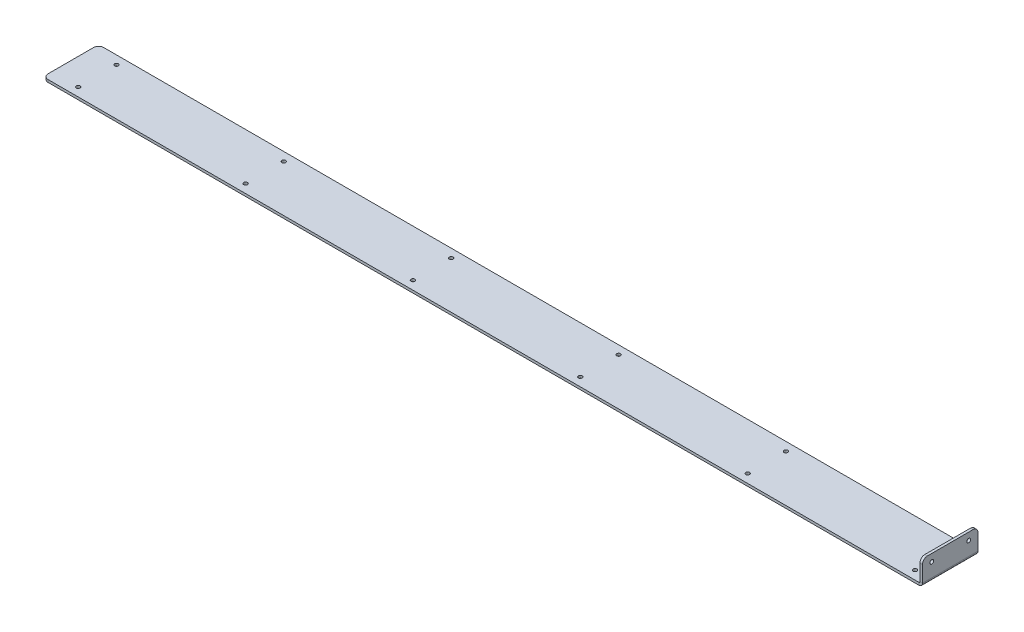
SolidWorks part; units mm, degrees
note: The reader was unsure of these and kept them because the rebuilt part matched: flange length of "Edge-Flange2".
material "5052-H32"
ref_plane "Front Plane" through (0, 0, 0) normal (0, 0, 1) x (1, 0, 0)
ref_plane "Top Plane" through (0, 0, 0) normal (0, 1, 0) x (1, 0, 0)
ref_plane "Right Plane" through (0, 0, 0) normal (1, 0, 0) x (0, 0, -1)
sketch "Sketch1" plane through (0, 0, 0) normal (0, 1, 0) x (1, 0, 0)
  line L1 (-1126.471, 35.7187) -> (0, 35.7188)
  line L2 (-1126.471, 35.7187) -> (-1126.471, -35.7188)
  line L3 (-1126.471, -35.7188) -> (0, -35.7188)
  line L4 (0, 35.7188) -> (0, -35.7188)
  point P4 (0, 0)
  dimension "D1" = 1126.471
  dimension "D2" = 71.4375
base flange "Base-Flange1" sketch "Sketch1" thickness 3.2639 reverse thickness direction no parameters "D1"=1.27
edge flange "Edge-Flange2" sketch "Sketch11" flange angle 90 flange length 31.75 flange position bend outside bend radius 1.27 thickness 3.2639 relief rectangular parameters "D6"=10
sketch "Sketch11" plane through (0, 0, 0) normal (1, 0, 0) x (0, 0, -1)
  line L2 (-35.7188, 0) -> (-35.7188, 28.4861)
  line L3 (-35.7188, 28.4861) -> (35.7187, 28.4861)
  line L4 (35.7187, 28.4861) -> (35.7188, 0)
  line L7 (-35.7188, 0) -> (35.7188, 0) construction
  line L8 (-35.7188, 0) -> (35.7188, 0)
bend "EdgeBend2" bend radius 1.27 bend angle 90 parameters "D5"=2
sketch "Sketch12" plane through (0, 0, 0) normal (0, 1, 0) x (1, 0, 0)
  line L0 (-16.1036, 24.6062) -> (-16.1036, -24.6062) construction
  line L1 (4.5339, 35.7187) -> (4.5339, -35.7188) construction
  point P2 (-16.1036, 0)
  dimension "D1" = 20.6375
  dimension "D2" = 49.2125
hole_wizard "#10 (0.1935) Diameter Hole1" positions "Sketch13" profile "Sketch14" hole size "#10" standard "ANSI Inch" end condition up to next
sketch "Sketch13" plane through (0, 0, 0) normal (0, 1, 0) x (1, 0, 0)
  point P0 (-16.1036, 24.6062)
  point P3 (-16.1036, -24.6062)
sketch "Sketch14" plane through (-16.1036, 0, -24.6062) normal (1, 0, 0) x (0, 0, 1)
  line L0 (0, 0) -> (0, 3.2639)
  line L1 (0, 3.2639) -> (2.4574, 3.2639)
  line L2 (2.4574, 3.2639) -> (2.4574, 0)
  line L5 (2.4574, 0) -> (0, 0)
  line L11 (0, -6.35) -> (0, 107.95) construction
  dimension "Thru Hole Dia." = 4.9149
  dimension "Thru Hole Depth" = 3.2639
pattern_linear "LPattern1" count 6 spacing 215.265 along (-1, 0, 0) of "#10 (0.1935) Diameter Hole1"
sketch "Sketch15" plane through (1.27, 0, 0) normal (-1, 0, 0) x (0, 0, 1)
  line L0 (23.8125, 19.05) -> (-23.8125, 19.05)
  line L1 (-35.7187, 0) -> (35.7187, 0) construction
  point P3 (0, 19.05)
  dimension "D1" = 47.625
  dimension "D2" = 19.05
hole_wizard "#10 (0.1935) Diameter Hole2" positions "Sketch17" profile "Sketch18" hole size "#10" standard "ANSI Inch" end condition up to next
sketch "Sketch17" plane through (1.27, 0, 0) normal (-1, 0, 0) x (0, 0, 1)
  point P0 (-23.8125, 19.05)
  point P3 (23.8125, 19.05)
sketch "Sketch18" plane through (1.27, 19.05, -23.8125) normal (0, 1, 0) x (0, 0, 1)
  line L0 (0, 0) -> (0, 3.2639)
  line L1 (0, 3.2639) -> (2.4574, 3.2639)
  line L2 (2.4574, 3.2639) -> (2.4574, 0)
  line L5 (2.4574, 0) -> (0, 0)
  line L11 (0, -6.35) -> (0, 107.95) construction
  dimension "Thru Hole Dia." = 4.9149
  dimension "Thru Hole Depth" = 3.2639
fillet "Fillet1" radius 6.35 4 edges at (-1126.471, -1.632, 35.7188) (-1126.471, -1.632, -35.7187) (2.902, 28.4861, 35.7188) (2.902, 28.4861, -35.7187)
sketch "Bend-Lines1" [suppressed] plane through (0, 0, 0) normal (0, 1, 0) x (1, 0, 0)
sketch "Bounding-Box1" [suppressed] plane through (0, 0, 0) normal (0, 1, 0) x (1, 0, 0)
sheet metal parameters "Sheet-Metal1" thickness 3.2639 parameters "D1"=1.27
flat pattern "Flat-Pattern1" [suppressed]
sketch "Bend-Lines2" plane through (0, 0, 0) normal (0, 1, 0) x (1, 0, 0)
sketch3d "Bounding-Box2" [suppressed]
  line L0 (0, -41.3639, 0) -> (1066.8, -41.3639, 0) construction
  line L1 (0, 41.3639, 0) -> (1066.8, 41.3639, 0) construction
  line L2 (0, -41.3639, 0) -> (0, 41.3639, 0) construction
  line L3 (1066.8, -41.3639, 0) -> (1066.8, 41.3639, 0) construction
sheet metal parameters "Sheet-Metal3" thickness 3.2639 parameters "D1"=1.27
flat pattern "Flat-Pattern1"
sketch "Bend-Lines2" plane through (0, 0, 0) normal (0, 1, 0) x (1, 0, 0)
  line L2 (2.2792, -38.1) -> (2.2792, 38.1) construction
  line L3 (2.2792, -38.1) -> (2.2792, 38.1) construction
sketch3d "Bounding-Box2" [suppressed]
  line L0 (50.8245, -38.1, 0) -> (-1103.5411, -38.1, 0) construction
  line L1 (50.8245, 38.1, 0) -> (-1103.5411, 38.1, 0) construction
  line L2 (50.8245, -38.1, 0) -> (50.8245, 38.1, 0) construction
  line L3 (-1103.5411, -38.1, 0) -> (-1103.5411, 38.1, 0) construction
bend of the flat pattern "Flatten-<EdgeBend2>1"
sheet metal parameters "Sheet-Metal4" thickness 3.2639 parameters "D1"=1.27
flat pattern "Flat-Pattern1"
sketch "Bend-Lines2" plane through (0, 0, 0) normal (0, 1, 0) x (1, 0, 0)
  line L2 (2.2792, -38.1) -> (2.2792, 38.1) construction
  line L3 (2.2792, -38.1) -> (2.2792, 38.1) construction
sketch3d "Bounding-Box2" [suppressed]
  line L0 (50.8245, -38.1, 0) -> (-1103.5411, -38.1, 0) construction
  line L1 (50.8245, 38.1, 0) -> (-1103.5411, 38.1, 0) construction
  line L2 (50.8245, -38.1, 0) -> (50.8245, 38.1, 0) construction
  line L3 (-1103.5411, -38.1, 0) -> (-1103.5411, 38.1, 0) construction
bend of the flat pattern "Flatten-<EdgeBend2>1"
sheet metal parameters "Sheet-Metal5" thickness 3.2639 parameters "D1"=1.27
flat pattern "Flat-Pattern1" [suppressed]
sketch "Bend-Lines2" plane through (0, 0, 0) normal (0, 1, 0) x (1, 0, 0)
  line L2 (2.2792, -38.1) -> (2.2792, 38.1) construction
  line L3 (2.2792, -38.1) -> (2.2792, 38.1) construction
sketch3d "Bounding-Box2" [suppressed]
  line L0 (50.8245, -38.1, 0) -> (-1111.4786, -38.1, 0) construction
  line L1 (50.8245, 38.1, 0) -> (-1111.4786, 38.1, 0) construction
  line L2 (50.8245, -38.1, 0) -> (50.8245, 38.1, 0) construction
  line L3 (-1111.4786, -38.1, 0) -> (-1111.4786, 38.1, 0) construction
bend of the flat pattern "Flatten-<EdgeBend2>1"
sketch "Sketch15-1" [suppressed] plane through (3.2884, 0, 0) normal (0, 1, 0) x (0, 0, 1)
  line L0 (25.4, 19.05) -> (-25.4, 19.05)
  line L1 (-38.1, -1114.767) -> (38.1, -1114.767)
  point P3 (0, 19.05)
  dimension "D1" = 50.8
  dimension "D2" = 1133.817
sheet metal parameters "Sheet-Metal6" thickness 3.2639 parameters "D1"=1.27
flat pattern "Flat-Pattern1" [suppressed]
sketch "Bend-Lines2" plane through (0, 0, 0) normal (0, 1, 0) x (1, 0, 0)
  line L2 (2.2792, -35.7187) -> (2.2792, 35.7187) construction
  line L3 (2.2792, -35.7187) -> (2.2792, 35.7187) construction
sketch3d "Bounding-Box2" [suppressed]
  line L0 (-1126.471, -35.7186, 0) -> (31.7745, -35.7188, 0) construction
  line L1 (-1126.4709, 35.7188, 0) -> (31.7745, 35.7186, 0) construction
  line L2 (-1126.471, -35.7186, 0) -> (-1126.4709, 35.7188, 0) construction
  line L3 (31.7745, -35.7188, 0) -> (31.7745, 35.7186, 0) construction
bend of the flat pattern "Flatten-<EdgeBend2>1"
sketch "Sketch15-1" [suppressed] plane through (3.2884, 0, 0) normal (0, 1, 0) x (0, 0, 1)
  line L0 (23.8125, 19.05) -> (-23.8125, 19.05)
  line L1 (-29.3687, -1129.7593) -> (29.3687, -1129.7593) construction
  point P3 (0, 19.05)
  dimension "D1" = 47.625
  dimension "D2" = 1148.8093
